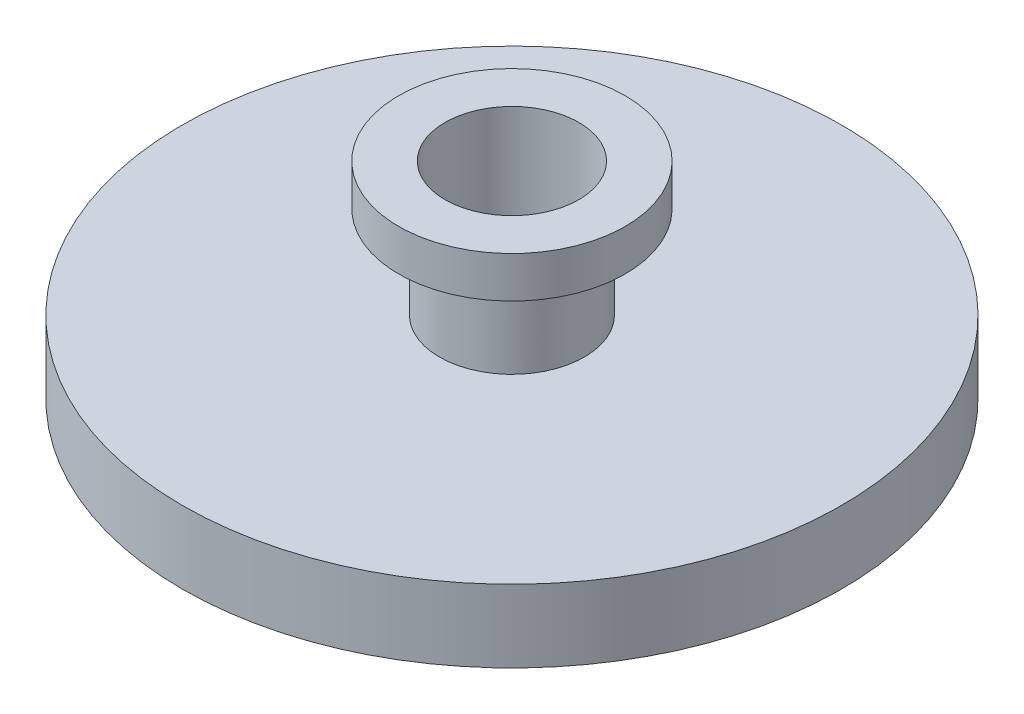
SolidWorks part; units mm, degrees
ref_plane "Front Plane" through (0, 0, 0) normal (0, 0, 1) x (1, 0, 0)
ref_plane "Top Plane" through (0, 0, 0) normal (0, 1, 0) x (1, 0, 0)
ref_plane "Right Plane" through (0, 0, 0) normal (1, 0, 0) x (0, 0, -1)
sketch "Sketch1" plane through (0, 0, 0) normal (0, 1, 0) x (1, 0, 0)
  circle A0 centre (0, 0) radius 101.6
  dimension "D1" = 203.2
extrude "Boss-Extrude1" add sketch "Sketch1" along normal blind 22.352
ref_plane "Plane1" through (0, 63.5, 0) normal (0, -1, 0) x (1, 0, 0)
sketch "Sketch2" plane through (0, 63.5, 0) normal (0, -1, 0) x (1, 0, 0)
  circle A0 centre (0, 0) radius 34.925
  dimension "D1" = 69.85
extrude "Boss-Extrude2" add sketch "Sketch2" along normal blind 12.7 separate body
sketch "Sketch3" plane through (0, 63.5, 0) normal (0, 1, 0) x (1, 0, 0)
  circle A0 centre (0, 0) radius 22.352
  dimension "D1" = 44.704
extrude "Boss-Extrude3" add sketch "Sketch3" against normal up to surface (41.148 mm away) up to face at (0, 22.352, 101.6)
sketch "Sketch4" plane through (0, 63.5, 0) normal (0, 1, 0) x (1, 0, 0)
  circle A0 centre (0, 0) radius 20.6375
  dimension "D1" = 41.275
extrude "Cut-Extrude1" cut sketch "Sketch4" against normal through all
